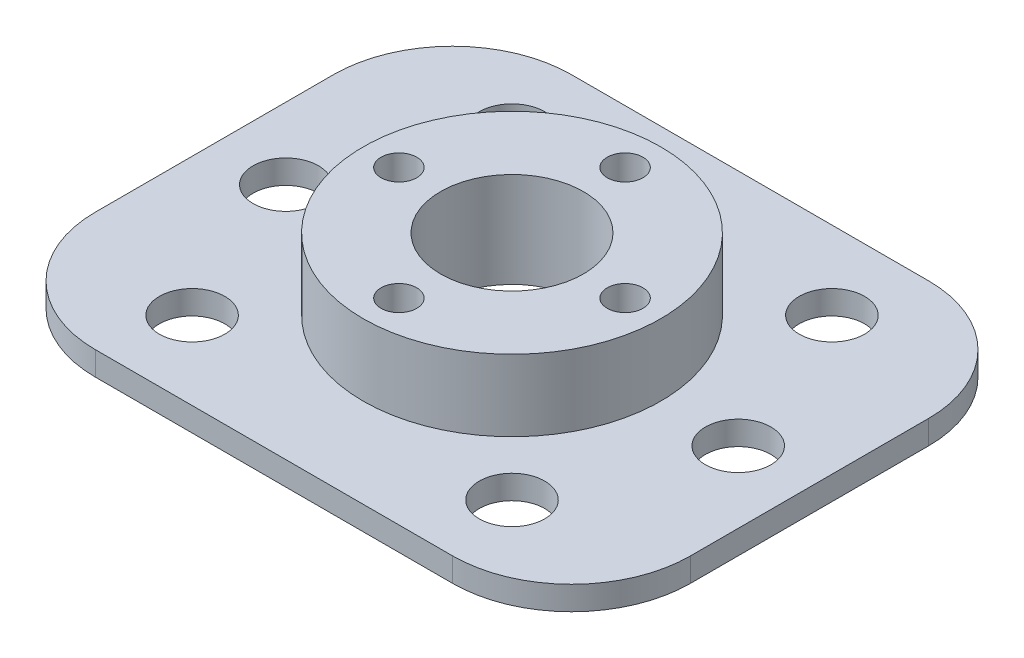
SolidWorks part; units mm, degrees
note: The reader was unsure of these and kept them because the rebuilt part matched: shared geometry of "Sketch1<3>".
ref_plane "Front Plane" through (0, 0, 0) normal (0, 0, 1) x (1, 0, 0)
ref_plane "Top Plane" through (0, 0, 0) normal (0, 1, 0) x (1, 0, 0)
ref_plane "Right Plane" through (0, 0, 0) normal (1, 0, 0) x (0, 0, -1)
sketch "Sketch1" plane through (0, 0, 0) normal (0, 1, 0) x (1, 0, 0)
  line L1 (-25, 20) -> (25, 20)
  line L2 (-25, 20) -> (-25, -20)
  line L3 (-25, -20) -> (25, -20)
  line L4 (25, 20) -> (25, -20)
  circle A0 centre (0, 0) radius 6
  circle A2 centre (0, 0) radius 19 construction
  circle A3 centre (13.435, -13.435) radius 2.75
  circle A4 centre (19, 0) radius 2.75
  circle A5 centre (13.435, 13.435) radius 2.75
  circle A6 centre (-13.435, 13.435) radius 2.75
  circle A7 centre (-19, 0) radius 2.75
  circle A8 centre (-13.435, -13.435) radius 2.75
  circle A9 centre (0, 0) radius 12.5
  point P4 (0, 20)
  point P6 (-25, 0)
  dimension "D3" = 12
  dimension "D4" = 25
  dimension "D1" = 40
  dimension "D2" = 50
extrude "Boss-Extrude1" add sketch "Sketch1" along normal blind 2 contours L4 L1 L2 L3 A9 A8 A7 A6 A5 A4 A3 | A9 A0
extrude "Boss-Extrude2" add sketch "Sketch1<3>" along normal blind 8 contours A9 A0
sketch "Sketch1<3>" plane through (0, 0, 0) normal (0, 1, 0) x (1, 0, 0) same geometry as "Sketch1"
hole_wizard "Hole1" positions "Sketch5" profile "Sketch4" legacy end condition up to next
sketch "Sketch5" plane through (0, 8, 0) normal (0, 1, 0) x (1, 0, 0)
  circle A0 centre (0, 0) radius 9.5 construction
  point P0 (0, -9.5)
  point P7 (0, 0)
  dimension "D1" = 19
sketch "Sketch4" plane through (0, 8, 9.5) normal (1, 0, 0) x (0, 0, 1)
  line L0 (0, 0) -> (0, 8)
  line L1 (0, 8) -> (1.5, 8)
  line L2 (1.5, 8) -> (1.5, 0)
  line L3 (1.5, 0) -> (0, 0)
  line L4 (0, 110) -> (0, -10) construction
  dimension "Diameter" = 3
  dimension "Depth" = 8
pattern_circular "CirPattern1" count 4 over 360 about axis through (0, 0, 0) along (0, 1, 0) of "Hole1"
fillet "Fillet1" radius 10 4 edges at (-25, 1, 20) (25, 1, 20) (-25, 1, -20) (25, 1, -20)
